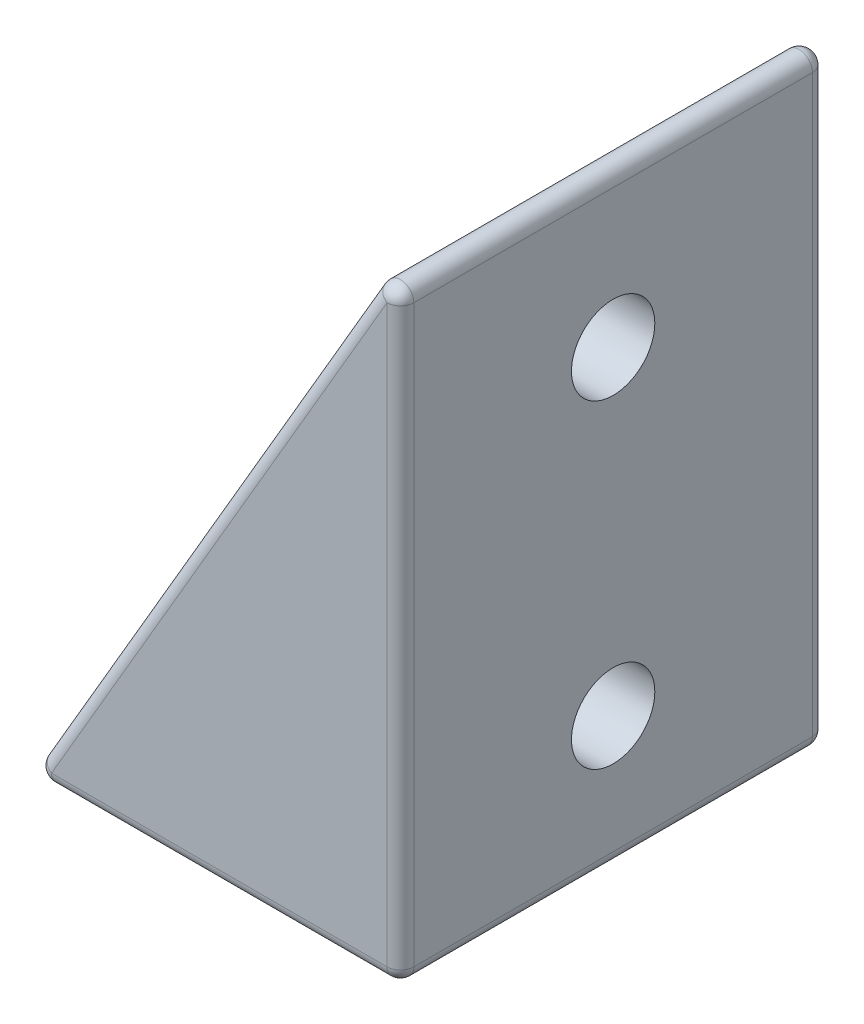
SolidWorks part; units mm, degrees
material "PET"
ref_plane "Front Plane" through (0, 0, 0) normal (0, 0, 1) x (1, 0, 0)
ref_plane "Top Plane" through (0, 0, 0) normal (0, 1, 0) x (1, 0, 0)
ref_plane "Right Plane" through (0, 0, 0) normal (1, 0, 0) x (0, 0, -1)
sketch "Sketch1" plane through (0, 0, 0) normal (0, 0, 1) x (1, 0, 0)
  line L0 (0, 0) -> (0, 38.1)
  line L1 (0, 38.1) -> (-22.225, 0)
  line L2 (-22.225, 0) -> (0, 0)
  dimension "D1" = 38.1
  dimension "D2" = 22.225
extrude "Boss-Extrude1" add sketch "Sketch1" along normal blind 25.4
fillet "Fillet1" radius 0.8 9 edges at (-11.1125, 0, 0) (0, 19.05, 0) (-11.1125, 19.05, 0) (-11.1125, 0, 25.4) (-11.1125, 19.05, 25.4) (-22.225, 0, 12.7) (0, 38.1, 12.7) (0, 0, 12.7) (0, 19.05, 25.4)
sketch "Sketch2" plane through (0, 0, 0) normal (1, 0, 0) x (0, 0, -1)
  line L0 (-0.8, 35.1409) -> (-24.6, 35.1409) construction
  circle A0 centre (-12.7, 26.8859) radius 2.4892
  circle A1 centre (-12.7, 7.8359) radius 2.4892
  point P6 (-12.7, 35.1409)
  dimension "D1" = 4.9784
  dimension "D2" = 8.255
  dimension "D3" = 19.05
extrude "Cut-Extrude1" cut sketch "Sketch2" against normal blind 50.8
